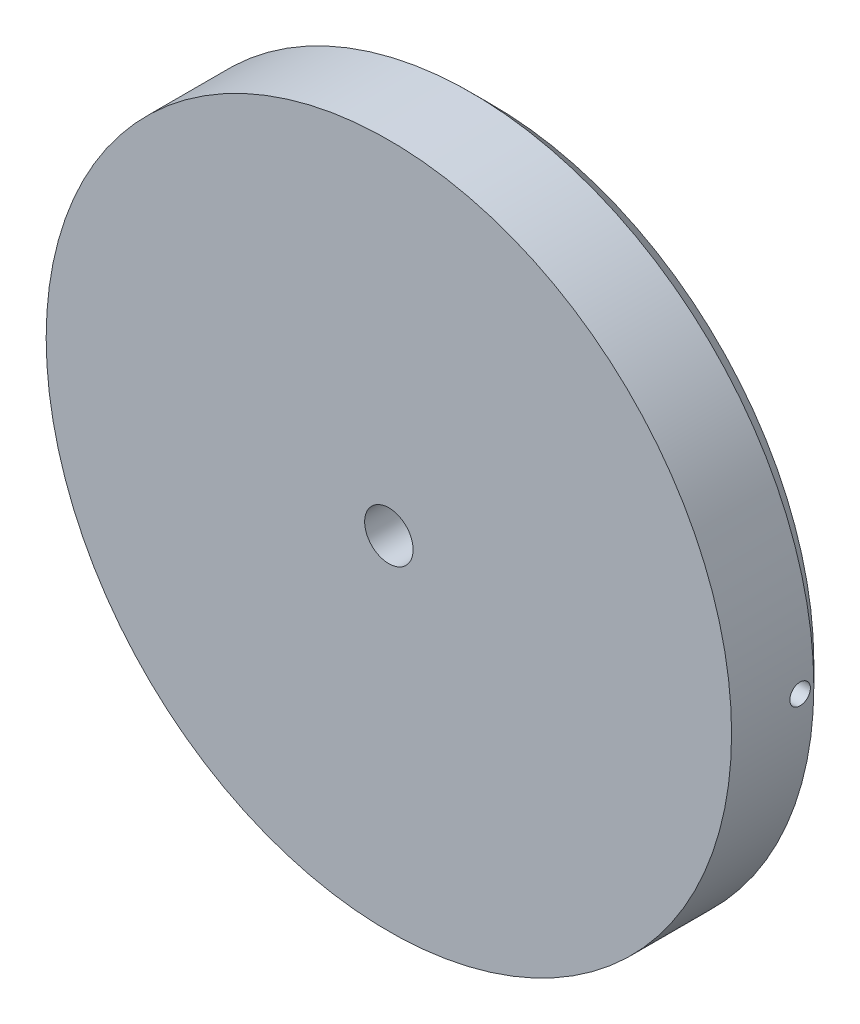
SolidWorks part; units mm, degrees
ref_plane "Front Plane" through (0, 0, 0) normal (0, 0, 1) x (1, 0, 0)
ref_plane "Top Plane" through (0, 0, 0) normal (0, 1, 0) x (1, 0, 0)
ref_plane "Right Plane" through (0, 0, 0) normal (1, 0, 0) x (0, 0, -1)
ref_axis "Z" through (0, 0, 543.0939) along (0, 0, -1)
ref_axis "X" through (17.0818, 0, 0) along (-1, 0, 0)
ref_axis "Y" through (0, 20.242, 0) along (0, -1, 0)
sketch "Sketch1" plane through (0, 0, 0) normal (0, 0, 1) x (1, 0, 0)
  circle A0 centre (0, 0) radius 50
  circle A1 centre (0, 0) radius 3.535
  dimension "D1" = 100
  dimension "D2" = 7.07
extrude "Boss-Extrude1" add sketch "Sketch1" against normal blind 5 and the other way blind 10
sketch "Sketch2" plane through (0, 0, 0) normal (0, 1, 0) x (1, 0, 0)
  line L0 (-16.3173, 0) -> (16.3173, 0) construction
  line L1 (0, -20.5521) -> (0, 20.5521) construction
  circle A0 centre (0, 0) radius 1.5
  dimension "D1" = 3
extrude "Cut-Extrude1" cut sketch "Sketch2" against normal through all
sketch "Sketch3" plane through (0, 0, 0) normal (1, 0, 0) x (0, 0, -1)
  circle A0 centre (0, 0) radius 1.5
  dimension "D1" = 3
extrude "Cut-Extrude2" cut sketch "Sketch3" along normal through all
chamfer "Chamfer1" distance 3 angle 45 1 edges at (50, 0, -5)
sketch "Sketch4" plane through (0, 0, 0) normal (0, 0, 1) x (1, 0, 0)
  circle A0 centre (0, 0) radius 3.535
  circle A2 centre (0, 0) radius 3.535 construction
  circle A3 centre (0, 0) radius 35
  dimension "D1" = 70
extrude "Boss-Extrude2" add sketch "Sketch4" along normal up to surface and the other way up to surface up to face at (50, 0, 10) other way up to face at (47, 0, -5)
sketch "Sketch5" plane through (0, 0, 0) normal (0, 0, 1) x (1, 0, 0)
  line L0 (0, 0) -> (0, -67) construction
  dimension "D1" = 67
ref_plane "Vert" through (0, 0, 0) normal (0.7071, 0.7071, 0) x (0, 0, -1)
equation "\"EyeDiameter\" = 100"
equation "\"BasePlaneDistance\" = \"EyeDiameter\"/2+\"L2Thickness\"+\"EyeClearance\""
equation "\"EyeClearance\" = 2"
equation "\"EyeOD\"= \"EyeDiameter\""
equation "\"D1@Sketch1\"=\"EyeOD\""
equation "\"D2@Sketch1\"= 7.07"
equation "\"pinHoleDiameter\"= 3"
equation "\"D1@Sketch2\"=\"pinHoleDiameter\""
equation "\"D1@Sketch3\"=\"pinHoleDiameter\""
equation "\"D1@Sketch4\"=\"EyeDiameter\"-30"
equation "\"D1@Sketch5\"=\"BasePlaneDistance\""
